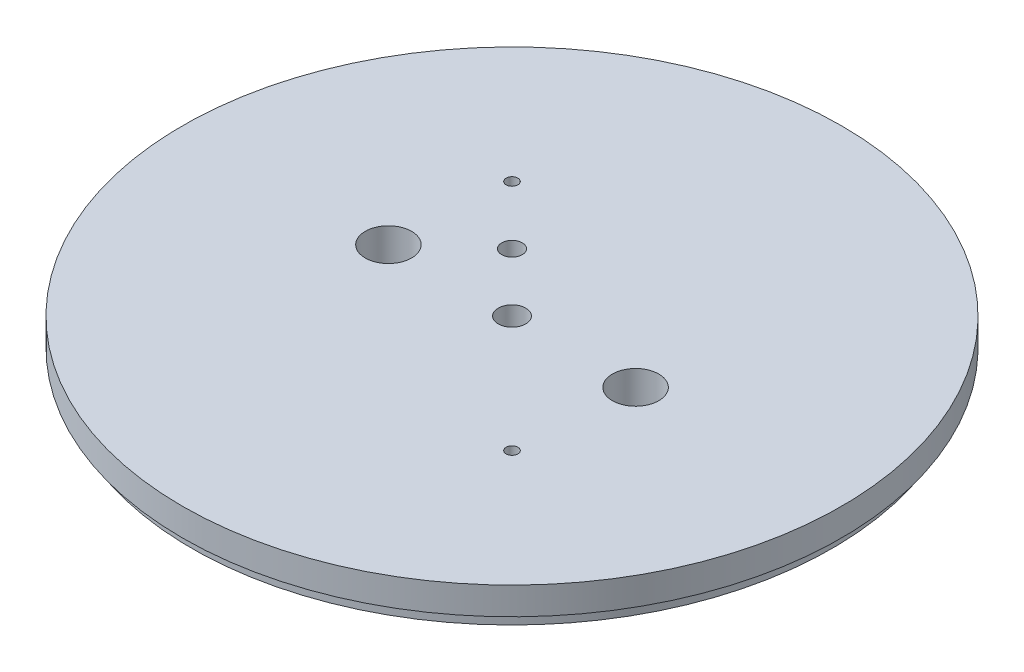
SolidWorks part; units mm, degrees
ref_plane "Front Plane" through (0, 0, 0) normal (0, 0, 1) x (1, 0, 0)
ref_plane "Top Plane" through (0, 0, 0) normal (0, 1, 0) x (1, 0, 0)
ref_plane "Right Plane" through (0, 0, 0) normal (1, 0, 0) x (0, 0, -1)
sketch "Sketch1" plane through (0, 0, 0) normal (0, 1, 0) x (1, 0, 0)
  line L0 (0, -76.2) -> (0, 76.2) construction
  line L1 (-76.2, 0) -> (76.2, 0) construction
  line L2 (-26.9408, 26.9408) -> (0, 0) construction
  line L3 (0, 56.7387) -> (0, 29.6936) construction
  line L4 (3.6407, 56.7387) -> (3.6407, 29.6936) construction
  line L5 (-3.6407, 56.7387) -> (-3.6407, 29.6936) construction
  line L6 (0, -56.7387) -> (0, -29.6936) construction
  line L7 (3.6407, -56.7387) -> (3.6407, -29.6936) construction
  line L8 (-3.6407, -56.7387) -> (-3.6407, -29.6936) construction
  line L9 (-53.8815, -53.8815) -> (54.3236, 54.3236) construction
  circle A0 centre (0, 0) radius 76.2
  circle A1 centre (0, 0) radius 3.175
  circle A2 centre (28.575, 0) radius 5.3578
  circle A3 centre (-28.575, 0) radius 5.3578
  circle A4 centre (-26.9408, 26.9408) radius 1.3589
  arc A6 (3.6407, 56.7387) -> (-3.6407, 56.7387) centre (0, 56.7387) ccw construction
  arc A7 (-3.6407, 29.6936) -> (3.6407, 29.6936) centre (0, 29.6936) ccw construction
  arc A8 (3.6407, -56.7387) -> (-3.6407, -56.7387) centre (0, -56.7387) cw construction
  arc A9 (-3.6407, -29.6936) -> (3.6407, -29.6936) centre (0, -29.6936) cw construction
  circle A10 centre (26.9408, -26.9408) radius 1.3589
  circle A11 centre (-13.4704, 13.4704) radius 2.3813
  point P16 (0, 43.2162)
  point P19 (0, 0)
  point P26 (0, -43.2162)
  dimension "D1" = 152.4
  dimension "D2" = 6.35
  dimension "D3" = 10.7156
  dimension "D5" = 2.7178
  dimension "D8" = 4.7625
  dimension "D6" = 38.1
  dimension "D7" = 45
  dimension "D4" = 45
  dimension "D9" = 28.575
extrude "Boss-Extrude1" add sketch "Sketch1" along normal blind 9.525
sketch "Sketch2" plane through (0, 0, 0) normal (0, -1, 0) x (1, 0, 0)
  circle A0 centre (0, 0) radius 76.2
  circle A1 centre (0, 0) radius 74.041
  dimension "D1" = 152.4
  dimension "D2" = 148.082
extrude "Cut-Extrude1" cut sketch "Sketch2" against normal blind 3.175
sketch "Sketch3" plane through (0, 9.525, 0) normal (0, 1, 0) x (1, 0, 0)
  line L0 (0, 76.2) -> (0, -76.2) construction
  line L1 (-76.2, 0) -> (76.2, 0) construction
  line L2 (0, 34.798) -> (0, 13.97) construction
  line L3 (3.2385, 34.798) -> (3.2385, 13.97)
  line L4 (-3.2385, 34.798) -> (-3.2385, 13.97)
  line L5 (0, -34.798) -> (0, -13.97) construction
  line L6 (3.2385, -34.798) -> (3.2385, -13.97)
  line L7 (-3.2385, -34.798) -> (-3.2385, -13.97)
  circle A0 centre (0, 0) radius 76.2 construction
  arc A1 (3.2385, 34.798) -> (-3.2385, 34.798) centre (0, 34.798) ccw
  arc A2 (-3.2385, 13.97) -> (3.2385, 13.97) centre (0, 13.97) ccw
  arc A3 (3.2385, -34.798) -> (-3.2385, -34.798) centre (0, -34.798) cw
  arc A4 (-3.2385, -13.97) -> (3.2385, -13.97) centre (0, -13.97) cw
  point P7 (0, 13.97)
  point P8 (0, 34.798)
  point P12 (0, 24.384)
  point P20 (0, -24.384)
  point P25 (0, -34.798)
  point P26 (0, -13.97)
  dimension "D1" = 13.97
  dimension "D2" = 20.828
  dimension "D3" = 6.477
extrude "Cut-Extrude2" cut sketch "Sketch3" against normal blind 3.556 from offset 5.969 offset against normal yes
equation "\"leadDist\"=1.5"
equation "\"Lead_Screw_Dist\" = 2.25in"
equation "\"D9@Sketch1\"=\"Lead_Screw_Dist\"/2"
equation "\"Lead_Screw_Diam\" = (27/64)*1in"
equation "\"D3@Sketch1\"=\"Lead_Screw_Diam\""
